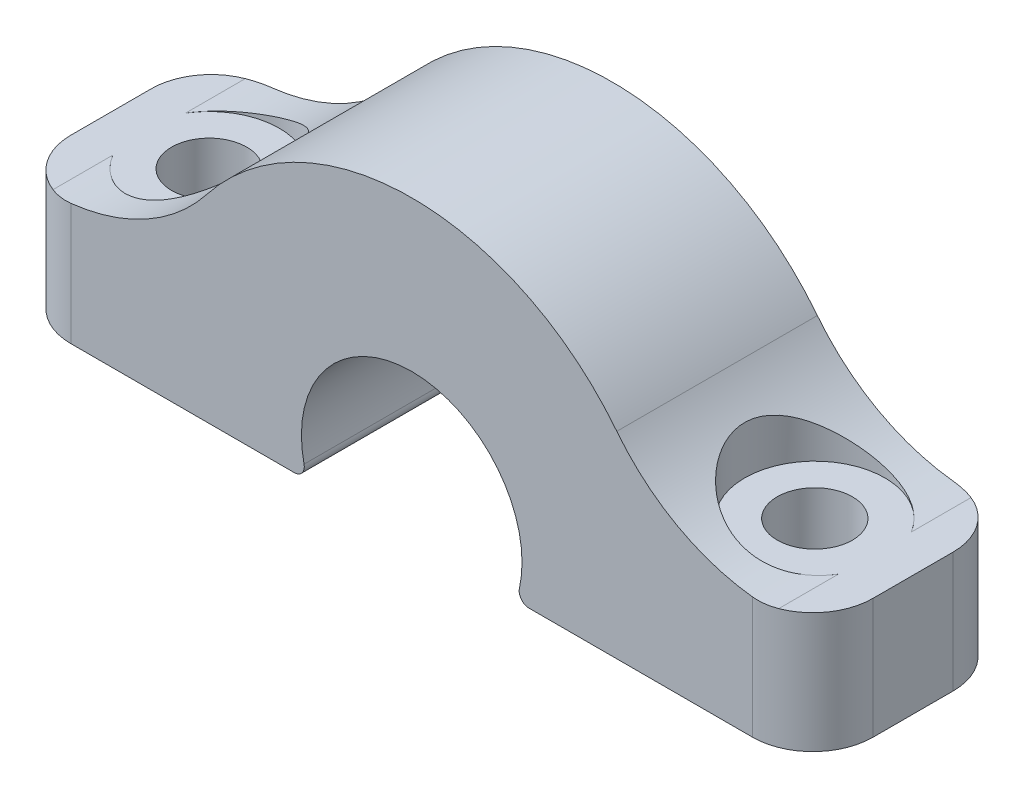
SolidWorks part; units mm, degrees
ref_plane "Front Plane" through (0, 0, 0) normal (0, 0, 1) x (1, 0, 0)
ref_plane "Top Plane" through (0, 0, 0) normal (0, 1, 0) x (1, 0, 0)
ref_plane "Right Plane" through (0, 0, 0) normal (1, 0, 0) x (0, 0, -1)
sketch "Sketch1" plane through (0, 0, 0) normal (0, 1, 0) x (1, 0, 0)
  line L1 (-20, 5) -> (20, 5)
  line L2 (-20, 5) -> (-20, -5)
  line L3 (-20, -5) -> (20, -5)
  line L4 (20, 5) -> (20, -5)
  line L5 (-20, 5) -> (20, -5) construction
  line L6 (-20, -5) -> (20, 5) construction
  point P0 (0, 0)
  dimension "D1" = 40
  dimension "D2" = 10
sketch "Sketch2" plane through (0, 0, 0) normal (0, 0, 1) x (1, 0, 0)
  line L0 (-4.7339, 0) -> (4.7339, 0) construction
  line L1 (0, -5.5) -> (0, 5.5) construction
  line L2 (-12.6949, 0) -> (12.6949, 0) construction
  line L3 (-12.6949, 0) -> (-4.7339, 0)
  line L4 (4.7339, 0) -> (12.6949, 0)
  arc A0 (-4.7339, 0) -> (4.7339, 0) centre (0, 2.8) cw
  arc A2 (-12.6949, 0) -> (12.6949, 0) centre (0, 2.8) cw
  point P3 (0, 2.8)
  point P4 (0, 0)
  point P5 (-4.7339, 0)
  point P6 (4.7339, 0)
  dimension "D4" = 13
  dimension "D1" = 2.8
  dimension "D2" = 5.5
  dimension "D3" = 5.5
extrude "Boss-Extrude1" add sketch "Sketch1" against normal blind 5 from offset 1 offset against normal yes
extrude "Boss-Extrude2" add sketch "Sketch2" along normal blind 5 and the other way blind 5
sketch "Sketch3" plane through (0, 0, 0) normal (0, 1, 0) x (1, 0, 0)
  line L0 (-13, -5) -> (13, -5) construction
  line L1 (-20, 5) -> (-10, 5)
  line L2 (-20, 5) -> (-20, -5)
  line L3 (-20, -5) -> (-10, -5)
  line L4 (-10, 5) -> (-10, -5)
  line L5 (0, -5.5) -> (0, 5.5) construction
  line L6 (20, -5) -> (10, -5)
  line L7 (20, 5) -> (20, -5)
  line L8 (20, 5) -> (10, 5)
  line L9 (10, 5) -> (10, -5)
  dimension "D1" = 10
extrude "Boss-Extrude3" add sketch "Sketch3" along normal blind 7
fillet "Fillet1" radius 3 4 edges at (20, 3.5, -5) (20, 3.5, 5) (-20, 3.5, -5) (-20, 3.5, 5)
fillet "Fillet2" radius 3 4 edges at (-20, -3.5, 5) (-20, -3.5, -5) (20, -3.5, 5) (20, -3.5, -5)
fillet "Fillet4" radius 10 2 edges at (12.3028, 7, 0) (-12.3028, 7, 0)
sketch "Sketch4" plane through (0, 0, 0) normal (0, 1, 0) x (1, 0, 0)
  line L0 (-10.7525, 0) -> (10.7525, 0) construction
  circle A0 centre (-15.1, 0) radius 1.875
  circle A1 centre (15.1, 0) radius 1.875
  dimension "D1" = 3.75
  dimension "D2" = 15.1
  dimension "D3" = 15.1
extrude "Cut-Extrude1" cut sketch "Sketch4" against normal through all both and the other way through all
sketch "Sketch5" plane through (0, 0, 0) normal (0, 1, 0) x (1, 0, 0)
  line L0 (0, -5.5) -> (0, 5.5) construction
  circle A0 centre (-15.1, 0) radius 3.5
  circle A1 centre (15.1, 0) radius 3.5
  dimension "D1" = 7
extrude "Cut-Extrude2" cut sketch "Sketch5" along normal blind 10 from offset 7
sketch "Sketch9" plane through (0, 0, 0) normal (0, 1, 0) x (1, 0, 0)
  line L1 (25.6287, -11.6641) -> (-21.4657, -11.6641)
  line L2 (25.6287, -11.6641) -> (25.6287, 11.6724)
  line L3 (25.6287, 11.6724) -> (-21.4657, 11.6724)
  line L4 (-21.4657, -11.6641) -> (-21.4657, 11.6724)
extrude "Cut-Extrude5" cut sketch "Sketch9" along normal blind 1
fillet "Fillet5" radius 0.5 2 edges at (-5.1971, 1, 0) (5.1971, 1, 0)
sketch "Sketch7" plane through (0, 0, 0) normal (0, 1, 0) x (1, 0, 0)
  line L5 (24.1582, -13.2438) -> (-27.5449, -13.2438)
  line L6 (24.1582, -13.2438) -> (24.1582, 9.8009)
  line L7 (24.1582, 9.8009) -> (-27.5449, 9.8009)
  line L8 (-27.5449, -13.2438) -> (-27.5449, 9.8009)
extrude "Cut-Extrude4" cut sketch "Sketch7" against normal through all
equation "\"shaftDiameter\"= 10mm"
equation "\"holeDiameter\"= 3.75mm"
equation "\"D1@Sketch4\"=\"holeDiameter\""
